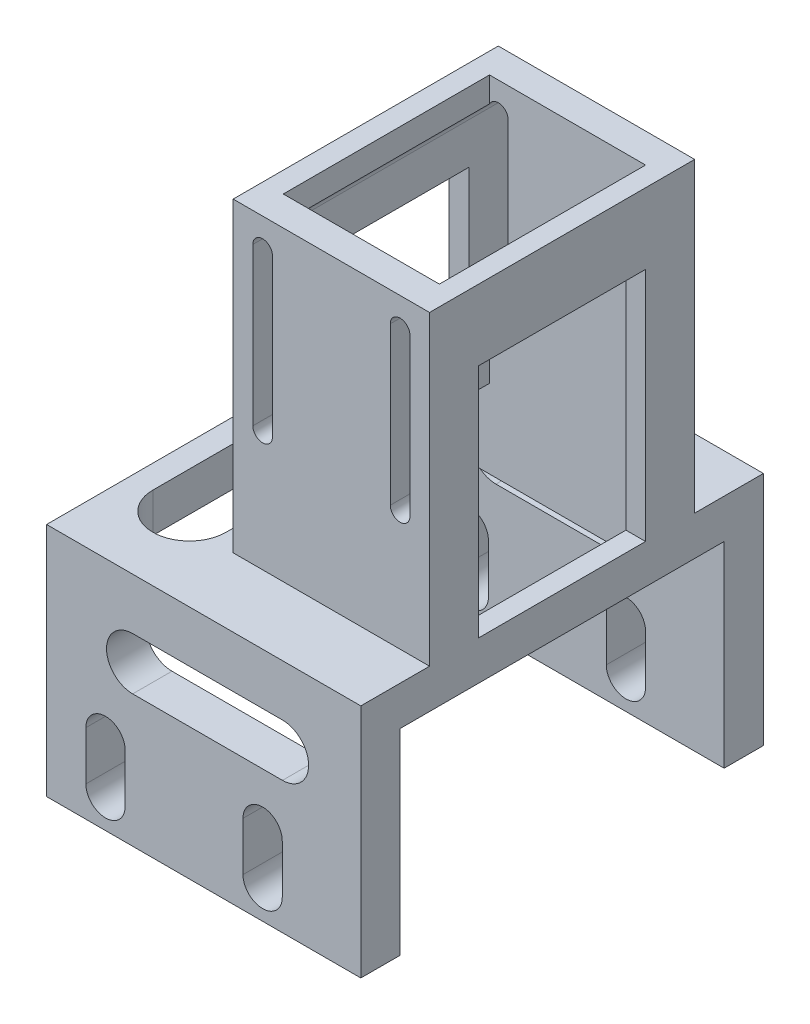
SolidWorks part; units mm, degrees
ref_plane "Front Plane" through (0, 0, 0) normal (0, 0, 1) x (1, 0, 0)
ref_plane "Top Plane" through (0, 0, 0) normal (0, 1, 0) x (1, 0, 0)
ref_plane "Right Plane" through (0, 0, 0) normal (1, 0, 0) x (0, 0, -1)
sketch "Sketch1" plane through (0, 0, 0) normal (0, 1, 0) x (1, 0, 0)
  line L1 (-25.4, 32.5437) -> (25.4, 32.5437)
  line L2 (-25.4, 32.5437) -> (-25.4, -32.5437)
  line L3 (-25.4, -32.5437) -> (25.4, -32.5437)
  line L4 (25.4, 32.5437) -> (25.4, -32.5437)
extrude "Boss-Extrude1" add sketch "Sketch1" along normal blind 6.35
sketch "Sketch2" plane through (0, 0, 0) normal (0, -1, 0) x (-1, 0, 0)
  line L0 (-25.4, -32.5437) -> (-25.4, 32.5437) construction
  line L1 (25.4, -32.5437) -> (-25.4, -32.5437)
  line L2 (25.4, -32.5437) -> (25.4, -26.1937)
  line L3 (25.4, -26.1937) -> (-25.4, -26.1938)
  line L4 (-25.4, -32.5437) -> (-25.4, -26.1938)
  line L6 (25.4, 32.5437) -> (-25.4, 32.5437)
  line L7 (25.4, 32.5437) -> (25.4, 26.1938)
  line L8 (25.4, 26.1938) -> (-25.4, 26.1938)
  line L9 (-25.4, 32.5437) -> (-25.4, 26.1938)
extrude "Boss-Extrude2" add sketch "Sketch2" along normal blind 31.75
sketch "Sketch4" plane through (0, 6.35, 0) normal (0, 1, 0) x (1, 0, 0)
  line L1 (22.225, -16.6687) -> (-3.0089, -16.6687)
  line L2 (22.225, -16.6687) -> (22.225, 16.6687)
  line L3 (22.225, 16.6687) -> (-3.0089, 16.6687)
  line L4 (-3.0089, -16.6687) -> (-3.0089, 16.6687)
extrude "Cut-Extrude1" cut sketch "Sketch4" against normal blind 31.75
sketch "Sketch5" plane through (0, 6.35, 0) normal (0, 1, 0) x (1, 0, 0)
  line L0 (25.4, -32.5437) -> (25.4, 32.5437) construction
  line L1 (-6.35, 21.4312) -> (25.4, 21.4312)
  line L2 (-6.35, 21.4312) -> (-6.35, -21.4312)
  line L3 (-6.35, -21.4312) -> (25.4, -21.4312)
  line L4 (25.4, 21.4312) -> (25.4, -21.4312)
extrude "Boss-Extrude3" add sketch "Sketch5" along normal blind 49.53
extrude "Cut-Extrude2" cut sketch "Sketch4<2>" along normal blind 58.7375
sketch "Sketch4<2>" plane through (0, 6.35, 0) normal (0, 1, 0) x (1, 0, 0) same geometry as "Sketch4"
sketch "Sketch7" plane through (0, 0, 21.4312) normal (0, 0, 1) x (1, 0, 0)
  line L0 (20.6375, 25.7175) -> (20.6375, 51.1175) construction
  line L1 (19.05, 25.7175) -> (19.05, 51.1175)
  line L2 (22.225, 25.7175) -> (22.225, 51.1175)
  line L4 (-1.5875, 51.1175) -> (-1.5875, 25.7175) construction
  line L5 (0, 51.1175) -> (0, 25.7175)
  line L6 (-3.175, 51.1175) -> (-3.175, 25.7175)
  arc A0 (19.05, 25.7175) -> (22.225, 25.7175) centre (20.6375, 25.7175) ccw
  arc A1 (22.225, 51.1175) -> (19.05, 51.1175) centre (20.6375, 51.1175) ccw
  arc A2 (0, 51.1175) -> (-3.175, 51.1175) centre (-1.5875, 51.1175) ccw
  arc A3 (-3.175, 25.7175) -> (0, 25.7175) centre (-1.5875, 25.7175) ccw
  point P2 (20.6375, 38.4175)
  point P7 (-1.5875, 38.4175)
extrude "Cut-Extrude4" cut sketch "Sketch7" against normal blind 58.7375
sketch "Sketch8" plane through (25.4, 0, 0) normal (1, 0, 0) x (0, 0, -1)
  line L1 (-13.4938, 44.45) -> (13.4937, 44.45)
  line L2 (-13.4938, 44.45) -> (-13.4937, 6.35)
  line L3 (-13.4937, 6.35) -> (13.4937, 6.35)
  line L4 (13.4937, 44.45) -> (13.4937, 6.35)
extrude "Cut-Extrude7" cut sketch "Sketch8" against normal blind 58.7375
sketch "Sketch12" plane through (0, 0, 0) normal (0, -1, 0) x (-1, 0, 0)
  line L1 (3.0089, 16.6687) -> (6.217, 16.6687)
  line L2 (3.0089, 16.6687) -> (3.0089, -13.4937)
  line L3 (3.0089, -13.4937) -> (6.217, -13.4937)
  line L4 (6.217, 16.6687) -> (6.217, -13.4937)
extrude "Cut-Extrude13" cut sketch "Sketch12" against normal blind 12.7
sketch "Sketch14" plane through (0, 0, 32.5437) normal (0, 0, 1) x (1, 0, 0)
  line L0 (9.525, -18.9193) -> (9.525, -26.8007) construction
  line L1 (12.7, -18.9193) -> (12.7, -26.8007)
  line L2 (6.35, -18.9193) -> (6.35, -26.8007)
  line L3 (-15.875, -18.9193) -> (-15.875, -26.8007) construction
  line L4 (-12.7, -18.9193) -> (-12.7, -26.8007)
  line L5 (-19.05, -18.9193) -> (-19.05, -26.8007)
  arc A0 (-12.7, -18.9193) -> (-19.05, -18.9193) centre (-15.875, -18.9193) ccw
  arc A1 (12.7, -18.9193) -> (6.35, -18.9193) centre (9.525, -18.9193) ccw
  arc A2 (6.35, -26.8007) -> (12.7, -26.8007) centre (9.525, -26.8007) ccw
  arc A3 (-19.05, -26.8007) -> (-12.7, -26.8007) centre (-15.875, -26.8007) ccw
  point P1 (-15.875, -22.86)
  point P2 (9.525, -22.86)
  point P14 (0, 0)
  point P15 (0, 0)
extrude "Cut-Extrude14" cut sketch "Sketch14" against normal blind 76.2
sketch "Sketch15" plane through (0, 0, 32.5437) normal (0, 0, 1) x (1, 0, 0)
  line L0 (-11.4816, -6.186) -> (12.7346, -6.186) construction
  line L1 (-11.4816, -1.9622) -> (12.7346, -1.9622)
  line L2 (-11.4816, -10.4097) -> (12.7346, -10.4097)
  arc A0 (-11.4816, -1.9622) -> (-11.4816, -10.4097) centre (-11.4816, -6.186) ccw
  arc A1 (12.7346, -10.4097) -> (12.7346, -1.9622) centre (12.7346, -6.186) ccw
  point P2 (0.6265, -6.186)
extrude "Cut-Extrude15" cut sketch "Sketch15" against normal blind 76.2
sketch "Sketch16" plane through (0, 6.35, 0) normal (0, 1, 0) x (1, 0, 0)
  line L0 (-15.7111, 19.1333) -> (-15.7111, -19.1333) construction
  line L1 (-9.7978, 19.1333) -> (-9.7978, -19.1333)
  line L2 (-21.6243, 19.1333) -> (-21.6243, -19.1333)
  arc A0 (-9.7978, 19.1333) -> (-21.6243, 19.1333) centre (-15.7111, 19.1333) ccw
  arc A1 (-21.6243, -19.1333) -> (-9.7978, -19.1333) centre (-15.7111, -19.1333) ccw
  point P2 (-15.7111, 0)
extrude "Cut-Extrude16" cut sketch "Sketch16" against normal blind 76.2
